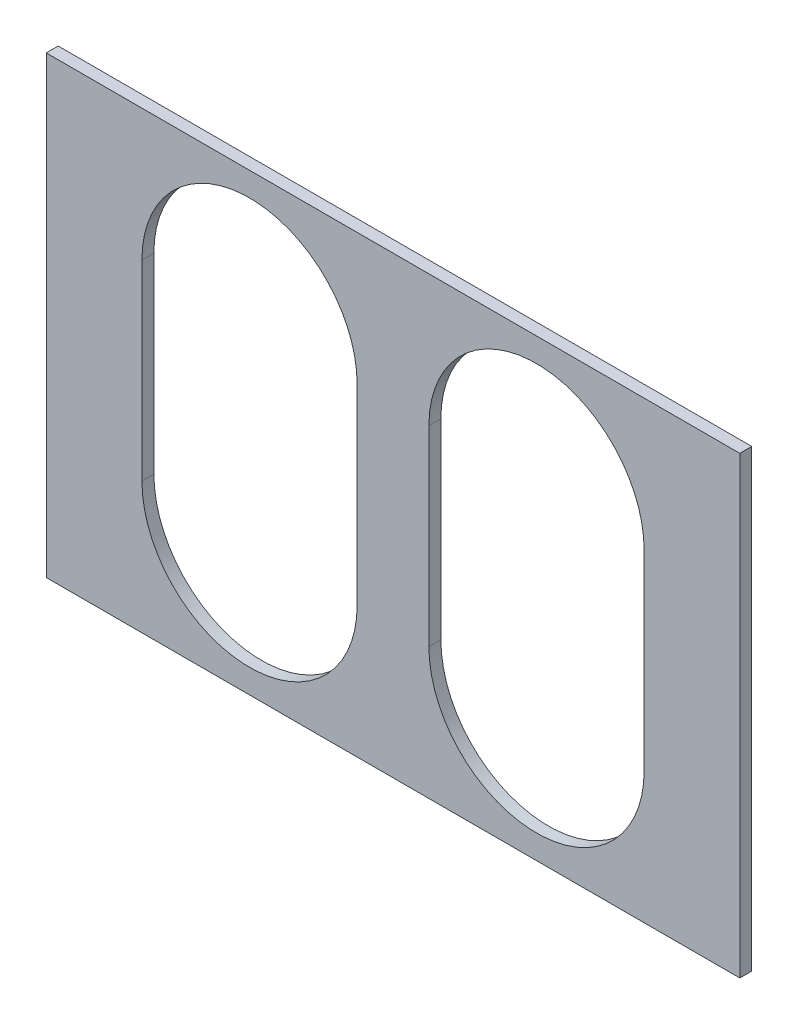
SolidWorks part; units mm, degrees
ref_plane "Спереди" through (0, 0, 0) normal (0, 0, 1) x (1, 0, 0)
ref_plane "Сверху" through (0, 0, 0) normal (0, 1, 0) x (1, 0, 0)
ref_plane "Справа" through (0, 0, 0) normal (1, 0, 0) x (0, 0, -1)
other "Configuration Table"
sketch "Эскиз1" plane through (0, 0, 0) normal (0, 0, 1) x (1, 0, 0)
  line L0 (-60, 40) -> (-60, -40) construction
  line L1 (145, 95) -> (-145, 95)
  line L2 (145, 95) -> (145, -95)
  line L3 (145, -95) -> (-145, -95)
  line L4 (-145, 95) -> (-145, -95)
  line L5 (145, 95) -> (-145, -95) construction
  line L6 (145, -95) -> (-145, 95) construction
  line L7 (-223.1783, 0) -> (249.0602, 0) construction
  line L8 (-15, 40) -> (-15, -40)
  line L9 (-105, 40) -> (-105, -40)
  line L10 (0, 83.5858) -> (0, -135.7738) construction
  line L11 (60, 40) -> (60, -40) construction
  line L12 (15, 40) -> (15, -40)
  line L13 (105, 40) -> (105, -40)
  arc A0 (-15, 40) -> (-105, 40) centre (-60, 40) ccw
  arc A1 (-105, -40) -> (-15, -40) centre (-60, -40) ccw
  arc A2 (15, 40) -> (105, 40) centre (60, 40) cw
  arc A3 (105, -40) -> (15, -40) centre (60, -40) cw
  point P0 (0, 0)
  point P10 (-60, 0)
  point P19 (60, 0)
  dimension "D1" = 190
  dimension "D2" = 290
  dimension "D3" = 90
  dimension "D4" = 170
  dimension "D5" = 15
  dimension "D6" = 145
extrude "Бобышка-Вытянуть1" add sketch "Эскиз1" along normal blind 5
sketch "Эскиз2" plane through (0, 0, 5) normal (0, 0, 1) x (1, 0, 0)
  line L8 (-15, -40) -> (-15, 40) construction
  line L9 (-15, 40) -> (15, 40)
  line L10 (-15, 40) -> (-15, -40)
  line L11 (-15, -40) -> (15, -40)
  line L12 (15, 40) -> (15, -40)
  line L13 (15, 40) -> (15, -40) construction
  point P8 (15, 0)
  dimension "D1" = 80
extrude "Бобышка-Вытянуть2" [suppressed] add sketch "Эскиз2" along normal blind 73
sketch "Эскиз3" [suppressed] plane through (-20, 0, 0) normal (-1, 0, 0) x (0, 0, 1)
  line L0 (78, 40) -> (78, -40) construction
  circle A0 centre (78, 0) radius 21.5
  dimension "D1" = 43
extrude "Вырез-Вытянуть1" [suppressed] cut sketch "Эскиз3" against normal up to surface (40 mm away) up to face at (15, 0, 2.5)
sketch "Эскиз4" plane through (-15, 0, 0) normal (-1, 0, 0) x (0, 0, 1)
  line L1 (16.5, -22.5) -> (49.5, -22.5) construction
  line L2 (16.5, -14) -> (49.5, -14)
  line L3 (16.5, -31) -> (49.5, -31)
  line L4 (-36.3542, 0) -> (121.0228, 0) construction
  line L5 (0, 95) -> (0, -95) construction
  line L6 (16.5, 22.5) -> (49.5, 22.5) construction
  line L7 (16.5, 14) -> (49.5, 14)
  line L8 (16.5, 31) -> (49.5, 31)
  arc A3 (16.5, -14) -> (16.5, -31) centre (16.5, -22.5) ccw
  arc A4 (49.5, -31) -> (49.5, -14) centre (49.5, -22.5) ccw
  arc A5 (16.5, 14) -> (16.5, 31) centre (16.5, 22.5) cw
  arc A6 (49.5, 31) -> (49.5, 14) centre (49.5, 22.5) cw
  point P7 (33, -22.5)
  point P15 (8, -22.5)
  point P20 (33, 22.5)
  dimension "D1" = 17
  dimension "D2" = 50
  dimension "D3" = 14
  dimension "D4" = 8
extrude "Вырез-Вытянуть2" [suppressed] cut sketch "Эскиз4" against normal up to surface (40 mm away) up to face at (15, 0, 2.5)
